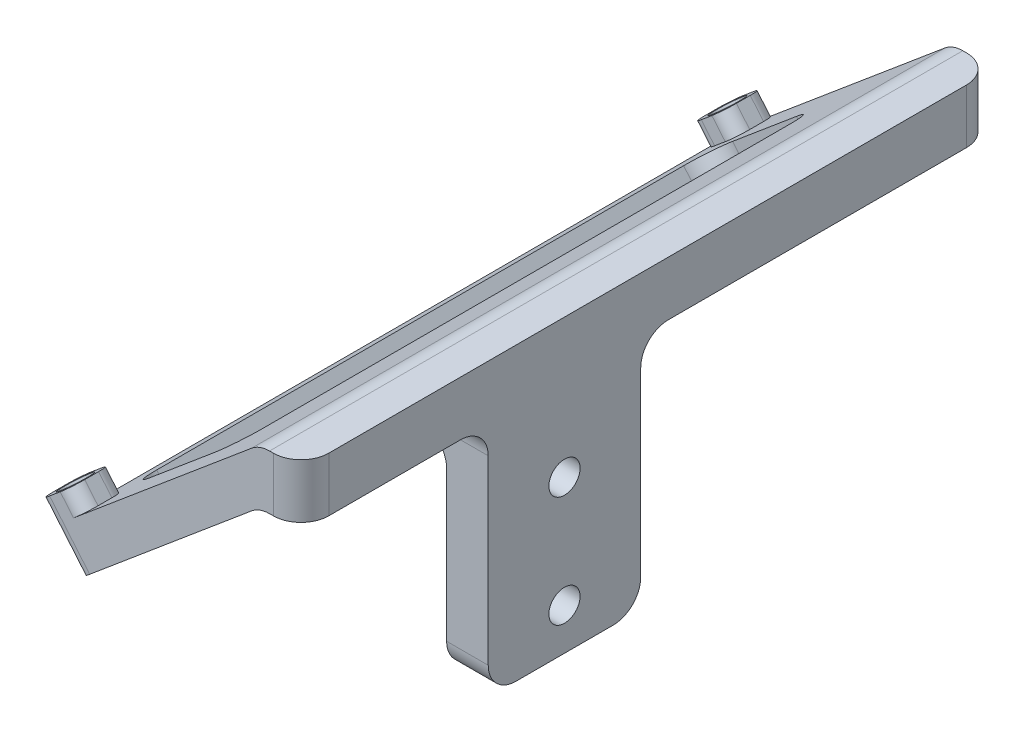
SolidWorks part; units mm, degrees
ref_plane "Front" through (0, 0, 0) normal (0, 0, 1) x (1, 0, 0)
ref_plane "Top" through (0, 0, 0) normal (0, 1, 0) x (1, 0, 0)
ref_plane "Right" through (0, 0, 0) normal (1, 0, 0) x (0, 0, -1)
sketch "Esquisse1" plane through (0, 0, 0) normal (0, 0, 1) x (1, 0, 0)
  line L0 (0, 0) -> (0, 34.1676)
  line L1 (0, 34.1676) -> (-26.019, 12.335)
  line L2 (-26.019, 12.335) -> (-29.8757, 16.9313)
  line L3 (-29.8757, 16.9313) -> (0, 42)
  line L4 (0, 42) -> (6, 42)
  line L5 (6, 42) -> (6, 0)
  line L6 (6, 0) -> (0, 0)
  line L7 (0, 34.1676) -> (0, 42) construction
  dimension "D1" = 6
  dimension "D2" = 6
  dimension "D3" = 50
  dimension "D4" = 42
  dimension "D5" = 39
extrude "Boss.-Extru.1" add sketch "Esquisse1" along normal blind 100
sketch "Esquisse2" plane through (-20.681, 24.6466, 0) normal (-0.6428, 0.766, 0) x (0.766, 0.6428, 0)
  line L0 (-12.0029, -50) -> (26.9971, -50) construction
  line L1 (-12.0029, -100) -> (-6.0029, -100)
  line L2 (-12.0029, -100) -> (-12.0029, -94)
  line L3 (-12.0029, -94) -> (-6.0029, -94)
  line L4 (-6.0029, -100) -> (-6.0029, -94)
  line L5 (-12.0029, -100) -> (-12.0029, 0) construction
  line L6 (26.9971, -100) -> (26.9971, 0) construction
  line L7 (-6.0029, 0) -> (-6.0029, -6)
  line L8 (-12.0029, -6) -> (-6.0029, -6)
  line L9 (-12.0029, 0) -> (-12.0029, -6)
  line L10 (-12.0029, 0) -> (-6.0029, 0)
  dimension "D1" = 6
  dimension "D2" = 6
extrude "Boss.-Extru.2" add sketch "Esquisse2" along normal blind 3
sketch "Esquisse3" plane through (-22.6093, 26.9447, 0) normal (-0.6428, 0.766, 0) x (0.766, 0.6428, 0)
  line L0 (-12.0029, -100) -> (-6.0029, -100) construction
  line L1 (-12.0029, -94) -> (-12.0029, -100) construction
  line L2 (-12.0029, -50) -> (26.9971, -50) construction
  line L3 (-12.0029, -94) -> (-12.0029, -6) construction
  line L4 (26.9971, -100) -> (26.9971, 0) construction
  circle A0 centre (-9.0029, -97) radius 2.25
  circle A1 centre (-9.0029, -3) radius 2.25
  point P4 (-9.0029, -100)
  dimension "D2" = 3
  dimension "D3" = 4.5
  dimension "D1" = 3
extrude "Enlèv. mat.-Extru.1" cut sketch "Esquisse3" against normal blind 5
sketch "Esquisse4" plane through (-19.3954, 23.1145, 0) normal (-0.6428, 0.766, 0) x (0.766, 0.6428, 0)
  circle A0 centre (-9.0029, -97) radius 1.75
  circle A1 centre (-9.0029, -3) radius 1.75
  dimension "D1" = 3.5
extrude "Enlèv. mat.-Extru.2" cut sketch "Esquisse4" against normal through all both and the other way through all
fillet "Congé1" radius 2 8 edges at (-28.9116, 15.7822, 0) (-26.2436, 21.9371, 0) (-26.2436, 21.9371, 6) (-30.8399, 18.0803, 6) (-30.8399, 18.0803, 94) (-26.2436, 21.9371, 94) (-26.2436, 21.9371, 100) (-28.9116, 15.7822, 100)
sketch "Esquisse5" plane through (6, 0, 0) normal (1, 0, 0) x (0, 0, -1)
  line L0 (-100, 34.1676) -> (0, 34.1676) construction
  line L1 (-100, 0) -> (-73, 0)
  line L2 (-100, 0) -> (-100, 34.1676)
  line L3 (-100, 34.1676) -> (-73, 34.1676)
  line L4 (-73, 0) -> (-73, 34.1676)
  line L6 (0, 0) -> (-51, 0)
  line L7 (0, 0) -> (0, 34.1676)
  line L8 (0, 34.1676) -> (-51, 34.1676)
  line L9 (-51, 0) -> (-51, 34.1676)
  dimension "D1" = 27
  dimension "D2" = 51
extrude "Enlèv. mat.-Extru.3" cut sketch "Esquisse5" against normal up to vertex (6 mm away) up to point (0, 34.1676, 100)
fillet "Congé2" radius 4 1 edges at (0, 34.1676, 62) tangent propagation no
sketch "Esquisse6" plane through (-20.681, 24.6466, 0) normal (-0.6428, 0.766, 0) x (0.766, 0.6428, 0)
  line L0 (-12.0029, -96) -> (-12.0029, -4) construction
  line L1 (-8.0029, -8) -> (11.9971, -8)
  line L2 (-8.0029, -8) -> (-8.0029, -92)
  line L3 (-8.0029, -92) -> (11.9971, -92)
  line L4 (11.9971, -8) -> (11.9971, -92)
  line L8 (-8.0029, -50) -> (-12.0029, -50) construction
  line L9 (-8.0029, -94) -> (-10.0029, -94) construction
  point P8 (0, 0)
  point P11 (-9.0029, -94)
  dimension "D1" = 4
  dimension "D2" = 20
  dimension "D3" = 2
extrude "Enlèv. mat.-Extru.5" cut sketch "Esquisse6" against normal up to vertex (6 mm away) up to point (-24.4869, 13.6206, 0)
fillet "Congé3" radius 4 13 edges at (0, 34.1676, 86.5) (0, 34.1676, 25.5) (0, 42, 50) (6, 38.0838, 0) (6, 38.0838, 100) (3, 34.1676, 51) (3, 34.1676, 73) (-9.5623, 30.0601, 92) (-24.8832, 17.2043, 92) (-24.8832, 17.2043, 8) (-9.5623, 30.0601, 8) (3, 0, 51) (3, 0, 73)
sketch "Esquisse7" plane through (6, 0, 0) normal (1, 0, 0) x (0, 0, -1)
  line L0 (-62, 0) -> (-62, 22) construction
  line L1 (-69, 0) -> (-55, 0) construction
  circle A0 centre (-62, 22) radius 2.25
  circle A1 centre (-62, 6) radius 2.25
  dimension "D1" = 16
  dimension "D2" = 4.5
  dimension "D3" = 6
extrude "Enlèv. mat.-Extru.6" cut sketch "Esquisse7" against normal up to vertex (6 mm away) up to point (0, 0, 55)
